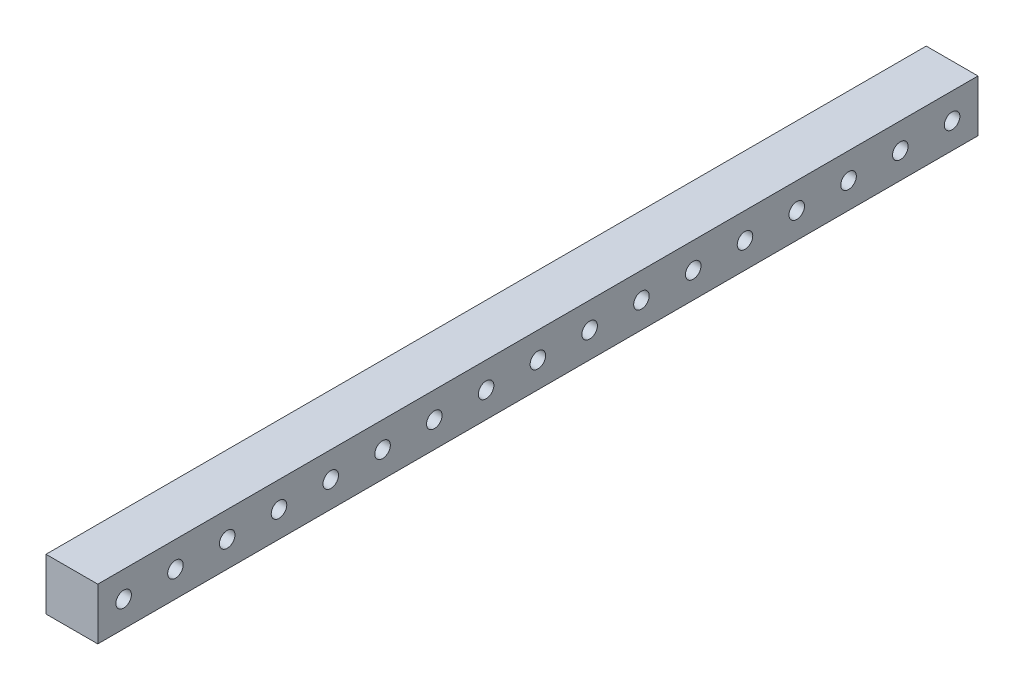
SolidWorks part; units mm, degrees
ref_plane "Front Plane" through (0, 0, 0) normal (0, 0, 1) x (1, 0, 0)
ref_plane "Top Plane" through (0, 0, 0) normal (0, 1, 0) x (1, 0, 0)
ref_plane "Right Plane" through (0, 0, 0) normal (1, 0, 0) x (0, 0, -1)
sketch "Sketch1" plane through (0, 0, 0) normal (0, 0, 1) x (1, 0, 0)
  line L0 (-10, -10) -> (10, 10) construction
  line L1 (-10, 10) -> (10, 10)
  line L2 (-10, 10) -> (-10, -10)
  line L3 (-10, -10) -> (10, -10)
  line L4 (10, 10) -> (10, -10)
  point P4 (0, 0)
  dimension "D1" = 20
  dimension "D2" = 45
extrude "Boss-Extrude1" add sketch "Sketch1" along normal blind 340
hole_wizard "Ø6.0mm Dowel Hole1" positions "Sketch2" profile "Sketch3" hole size "Ø6.0" standard "ANSI Metric" end condition through all
sketch "Sketch2" plane through (10, 0, 0) normal (1, 0, 0) x (0, 0, -1)
  line L0 (0, -10) -> (0, 10) construction
  point P0 (-10, 0)
  point P7 (0, 0)
  dimension "D1" = 10
sketch "Sketch3" plane through (10, 0, 10) normal (0, 1, 0) x (0, 0, -1)
  line L0 (0, 0) -> (0, 20)
  line L1 (0, 20) -> (3, 20)
  line L2 (3, 20) -> (3, 0)
  line L5 (3, 0) -> (0, 0)
  line L11 (0, -6.35) -> (0, 107.95) construction
  dimension "Thru Hole Dia." = 6
  dimension "Thru Hole Depth" = 20
pattern_linear "LPattern2" count 17 spacing 20 along (0, 0, 1) of "Ø6.0mm Dowel Hole1"
